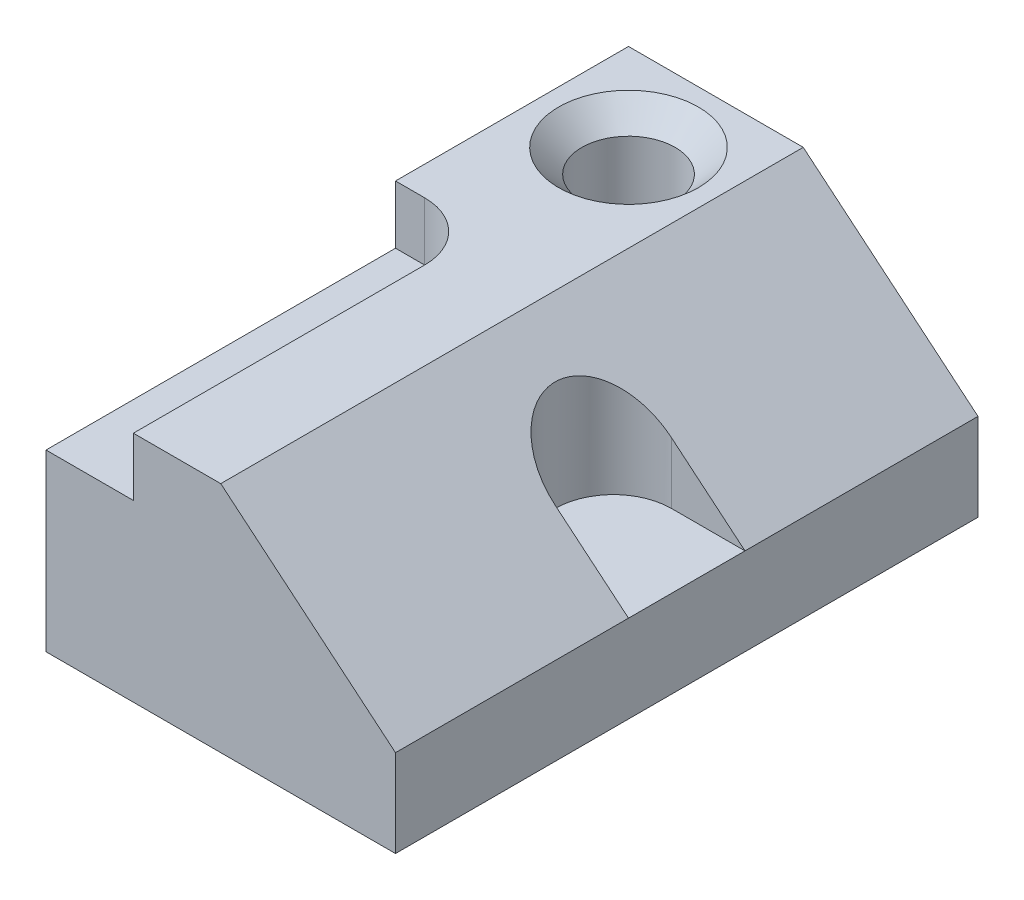
SolidWorks part; units mm, degrees
material "Plain Carbon Steel"
ref_plane "Front Plane" through (0, 0, 0) normal (0, 0, 1) x (1, 0, 0)
ref_plane "Top Plane" through (0, 0, 0) normal (0, 1, 0) x (1, 0, 0)
ref_plane "Right Plane" through (0, 0, 0) normal (1, 0, 0) x (0, 0, -1)
sketch "Sketch1" plane through (0, 0, 0) normal (0, 0, 1) x (1, 0, 0)
  line L0 (0, 0) -> (76.2, 0)
  line L1 (76.2, 0) -> (76.2, 19.05)
  line L2 (76.2, 19.05) -> (38.1, 50.8)
  line L3 (38.1, 50.8) -> (0, 50.8)
  line L4 (0, 50.8) -> (0, 0)
  point P8 (86.1637, -51.97)
  dimension "D1" = 38.1
  dimension "D2" = 19.05
  dimension "D3" = 76.2
  dimension "D4" = 50.8
extrude "Boss-Extrude1" add sketch "Sketch1" along normal blind 127
sketch3d "3DSketch1"
  circle A0 centre (19.05, 50.8, 19.05) radius 10.16
  point P2 (19.05, 60.96, 19.05)
  point P3 (0, 50.8, 0)
  point P5 (0, 0, 0)
  point P6 (0, 50.8, 0)
  point P8 (0, 0, 0)
  point P10 (0, 50.8, 0)
  dimension "D3" = 20.32
  dimension "D1" = 19.05
  dimension "D2" = 19.05
extrude "Cut-Extrude3" cut sketch "3DSketch1" along direction (0, 1, 0) on the side against the normal through all
chamfer "Chamfer3" distance 5.08 angle 45 2 edges at (19.05, 0, 29.21) (19.05, 50.8, 29.21)
sketch "Sketch2" plane through (0, 50.8, 0) normal (0, 1, 0) x (1, 0, 0)
  line L1 (0, -127) -> (19.05, -127)
  line L2 (0, -127) -> (0, -50.8)
  line L3 (0, -50.8) -> (19.05, -50.8)
  line L4 (19.05, -127) -> (19.05, -50.8)
  dimension "D1" = 76.2
  dimension "D2" = 19.05
extrude "Cut-Extrude4" cut sketch "Sketch2" against normal blind 12.7
fillet "Fillet2" radius 12.7 1 edges at (19.05, 44.45, 50.8) type face fillet first side face at (9.525, 44.45, 50.8) second side face at (19.05, 44.45, 88.9)
sketch "Sketch3" plane through (0, 50.8, 0) normal (0, 1, 0) x (1, 0, 0)
  line L0 (76.2, -50.8) -> (60.198, -50.8)
  line L1 (76.2, -127) -> (76.2, 0) construction
  line L2 (60.198, -76.2) -> (76.2, -76.2)
  line L3 (76.2, -63.5) -> (0, -63.5) construction
  line L4 (0, -50.8) -> (0, -127) construction
  line L5 (76.2, -50.8) -> (76.2, -76.2)
  arc A0 (60.198, -50.8) -> (60.198, -76.2) centre (60.198, -63.5) ccw
  point P6 (47.498, -63.5)
  dimension "D1" = 16.002
  dimension "D2" = 12.7
extrude "Cut-Extrude10" cut sketch "Sketch3" against normal up to vertex (31.75 mm away) up to point (76.2, 19.05, 127)
